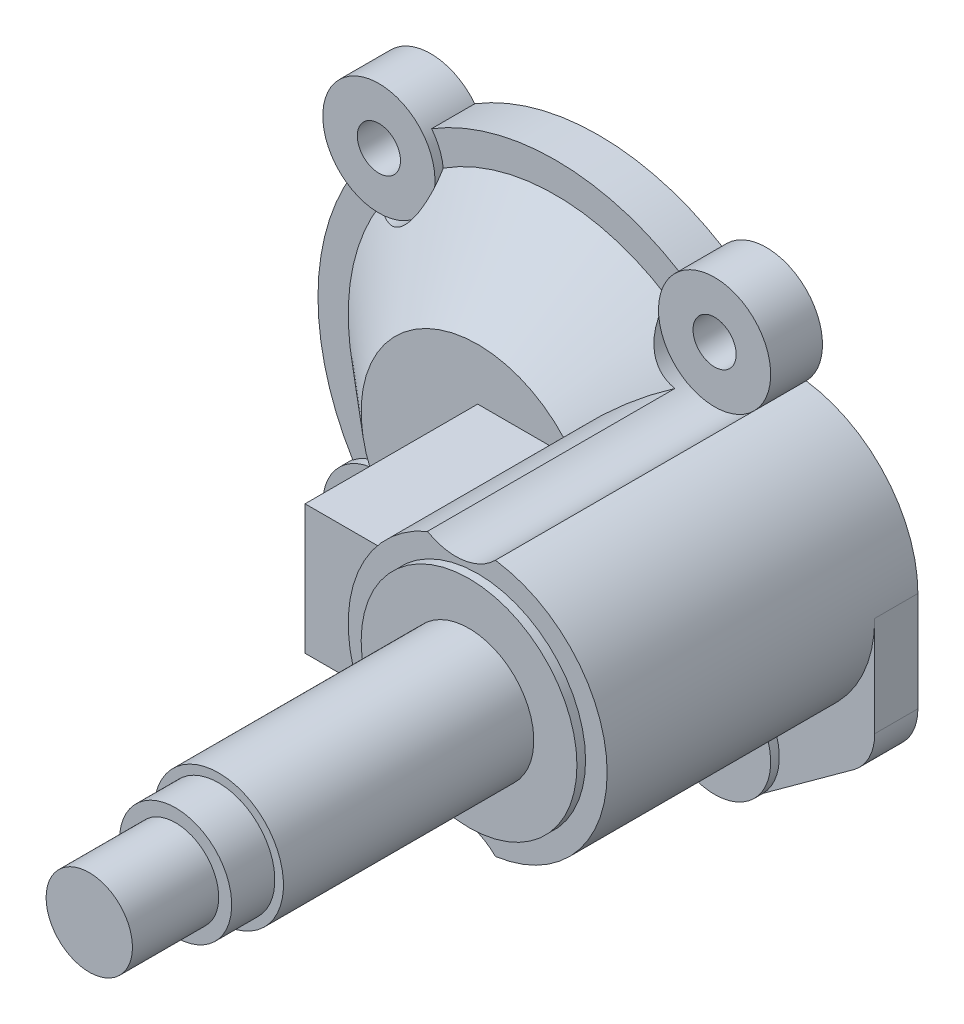
SolidWorks part; units mm, degrees
ref_plane "Front Plane" through (0, 0, 0) normal (1, 0, 0) x (0, 1, 0)
ref_plane "Top Plane" through (0, 0, 0) normal (0, 0, 1) x (0, 1, 0)
ref_plane "Right Plane" through (0, 0, 0) normal (0, 1, 0) x (-1, 0, 0)
sketch "Sketch1" plane through (0, 0, 0) normal (0, 0, 1) x (0, 1, 0)
  line L1 (-19.4454, 19.4454) -> (19.4454, 19.4454) construction
  line L2 (-19.4454, 19.4454) -> (-19.4454, -19.4454) construction
  line L3 (-19.4454, -19.4454) -> (19.4454, -19.4454) construction
  line L4 (19.4454, 19.4454) -> (19.4454, -19.4454) construction
  line L5 (-19.4454, 19.4454) -> (19.4454, -19.4454) construction
  line L6 (-19.4454, -19.4454) -> (19.4454, 19.4454) construction
  circle A0 centre (0, 0) radius 27.5
  circle A1 centre (19.4454, 19.4454) radius 6.5
  circle A2 centre (-19.4454, 19.4454) radius 6.5
  circle A3 centre (-19.4454, -19.4454) radius 6.5
  circle A4 centre (19.4454, -19.4454) radius 6.5
  circle A5 centre (-19.4454, 19.4454) radius 2.5
  circle A6 centre (19.4454, 19.4454) radius 2.5
  circle A7 centre (19.4454, -19.4454) radius 2.5
  circle A8 centre (-19.4454, -19.4454) radius 2.5
  dimension "D1" = 55
  dimension "D2" = 13
  dimension "D3" = 5
extrude "Boss-Extrude1" add sketch "Sketch1" against normal blind 5 contours A0 A2 | A0 A2 | A4 A0 A1 A2 A3 | A0 A3 | A0 A3 | A0 A4 | A0 A4 | A0 A1 | A0 A1 region at (0, 0, 0) region at (-17.1693, 17.1693, 0) region at (-21.4818, 21.4818, 0) region at (21.4818, 21.4818, 0) region at (17.1693, 17.1693, 0) region at (-17.1693, -17.1693, 0) region at (-21.4818, -21.4818, 0) region at (21.4818, -21.4818, 0) region at (17.1693, -17.1693, 0)
sketch "Sketch5" plane through (0, 0, 0) normal (1, 0, 0) x (0, 1, 0)
  line L0 (0, 0) -> (24, 0)
  line L1 (24, 0) -> (13.5, 9)
  line L2 (13.5, 9) -> (0, 9)
  line L3 (0, 9) -> (0, 0)
  dimension "D1" = 13.5
  dimension "D2" = 24
  dimension "D3" = 9
revolve "Revolve1" add sketch "Sketch5" angle 360 about L3
sketch "Sketch6" plane through (0, 0, -5) normal (0, 0, -1) x (0, 1, 0)
  line L0 (-24.0416, 24.0416) -> (-14.6268, 37)
  line L1 (-14.6268, 37) -> (0, 37)
  line L2 (0, 37) -> (0, 27.5)
  arc A0 (-14.3383, 23.4662) -> (-23.4662, 14.3383) centre (-19.4454, 19.4454) ccw construction
  arc A1 (14.3383, 23.4662) -> (-14.3383, 23.4662) centre (0, 0) ccw construction
  circle A2 centre (0, 22) radius 15
  arc A10 (23.4662, 14.3383) -> (14.3383, 23.4662) centre (19.4454, 19.4454) ccw
  arc A11 (14.3383, 23.4662) -> (-14.3383, 23.4662) centre (0, 0) ccw
  arc A12 (-14.3383, 23.4662) -> (-23.4662, 14.3383) centre (-19.4454, 19.4454) ccw
  arc A13 (-23.4662, 14.3383) -> (-23.4662, -14.3383) centre (0, 0) ccw
  arc A14 (-23.4662, -14.3383) -> (-14.3383, -23.4662) centre (-19.4454, -19.4454) ccw
  arc A15 (-14.3383, -23.4662) -> (14.3383, -23.4662) centre (0, 0) ccw
  arc A16 (14.3383, -23.4662) -> (23.4662, -14.3383) centre (19.4454, -19.4454) ccw
  arc A17 (23.4662, -14.3383) -> (23.4662, 14.3383) centre (0, 0) ccw
  arc A18 (23.4662, 14.3383) -> (14.3383, 23.4662) centre (19.4454, 19.4454) ccw
  arc A19 (14.3383, 23.4662) -> (-14.3383, 23.4662) centre (0, 0) ccw
  arc A20 (-14.3383, 23.4662) -> (-23.4662, 14.3383) centre (-19.4454, 19.4454) ccw
  arc A21 (-23.4662, 14.3383) -> (-23.4662, -14.3383) centre (0, 0) ccw
  arc A22 (-23.4662, -14.3383) -> (-14.3383, -23.4662) centre (-19.4454, -19.4454) ccw
  arc A23 (-14.3383, -23.4662) -> (14.3383, -23.4662) centre (0, 0) ccw
  arc A24 (14.3383, -23.4662) -> (23.4662, -14.3383) centre (19.4454, -19.4454) ccw
  arc A25 (23.4662, -14.3383) -> (23.4662, 14.3383) centre (0, 0) ccw
  arc M11 (23.4662, 14.3383) -> (14.3383, 23.4662) centre (19.4454, 19.4454) ccw
  arc M12 (14.3383, 23.4662) -> (-14.3383, 23.4662) centre (0, 0) ccw
  arc M13 (-14.3383, 23.4662) -> (-23.4662, 14.3383) centre (-19.4454, 19.4454) ccw
  dimension "D3" = 30
  dimension "D2" = 36
  dimension "D4" = 22
  dimension "D1" = 0
extrude "Boss-Extrude2" add sketch "Sketch6" against normal up to surface (5 mm away) contours L2 A2 M13 M12 | A2 L2 M11 M12 | A2 L1 L0 M13 | A2 M13 M11 M12 region at (31.483, -14.5037, -5) region at (17.8507, 0, -5) region at (30.5569, -6.4562, -5) region at (30.5569, 6.4562, -5) up to face at (0, -24, 0)
sketch "Sketch7" plane through (0, 0, 0) normal (0, 1, 0) x (-1, 0, 0)
  line L0 (-22, 0) -> (-22, 76)
  line L1 (-22, 76) -> (-27, 76)
  line L2 (-27, 76) -> (-27, 66)
  line L3 (-27, 66) -> (-28.5, 66)
  line L4 (-28.5, 66) -> (-28.5, 61)
  line L5 (-28.5, 61) -> (-29.5, 61)
  line L6 (-29.5, 61) -> (-29.5, 32)
  line L7 (-29.5, 32) -> (-34.5, 32)
  line L8 (-34.5, 32) -> (-34.5, 31)
  line L9 (-34.5, 31) -> (-37, 31)
  line L10 (-37, 31) -> (-37, 0)
  line L11 (-37, 0) -> (-22, 0)
  line L12 (-24.0514, 0) -> (-37, 0) construction
  line L13 (-14.3383, -5) -> (14.3383, -5) construction
  line L14 (-37, 0) -> (-37, -5) construction
  dimension "D1" = 22
  dimension "D2" = 10
  dimension "D3" = 5
  dimension "D4" = 29
  dimension "D5" = 1
  dimension "D6" = 36
  dimension "D7" = 12.5
  dimension "D8" = 7.5
  dimension "D9" = 6.5
  dimension "D10" = 5
revolve "Revolve2" add sketch "Sketch7" angle 360 about L0
sketch "Sketch8" plane through (0, 0, 9) normal (0, 0, 1) x (1, 0, 0)
  line L1 (0, 7.5) -> (9.0096, 7.5)
  line L2 (0, 7.5) -> (0, -7.5)
  line L3 (0, -7.5) -> (9.0096, -7.5)
  line L4 (9.0096, 7.5) -> (9.0096, -7.5)
  circle A0 centre (22, 0) radius 15 construction
  point P4 (8.4213, -6.3732)
  point P7 (0, 0)
  dimension "D1" = 15
extrude "Boss-Extrude3" add sketch "Sketch8" along normal blind 20
extrude "Cut-Extrude1" cut sketch "Sketch1<3>" along normal through all contours A8 A0 A3 | A7 A0 A4 | A6 A0 A1 | A5 A0 A2 | A3 | A4 region at (-17.1693, 17.1693, 0) region at (17.1693, 17.1693, 0) region at (-17.1693, -17.1693, 0) region at (17.1693, -17.1693, 0)
sketch "Sketch1<3>" plane through (0, 0, 0) normal (0, 0, 1) x (0, 1, 0) same geometry as "Sketch1"
fillet "Fillet1" radius 6 1 edges at (37, -14.6268, -2.5)
extrude "Boss-Extrude4" add sketch "Sketch1<4>" along normal blind 1 contours A8 A0 A3 | A8 A0 A3 | A5 A0 A2 | A5 A0 A2 | A6 A0 A1 | A6 A0 A1 | A7 A0 A4 | A7 A0 A4 region at (-17.1693, 17.1693, 0) region at (-21.4818, 21.4818, 0) region at (21.4818, 21.4818, 0) region at (17.1693, 17.1693, 0) region at (-17.1693, -17.1693, 0) region at (-21.4818, -21.4818, 0) region at (21.4818, -21.4818, 0) region at (17.1693, -17.1693, 0)
sketch "Sketch1<4>" plane through (0, 0, 0) normal (0, 0, 1) x (0, 1, 0) same geometry as "Sketch1"
